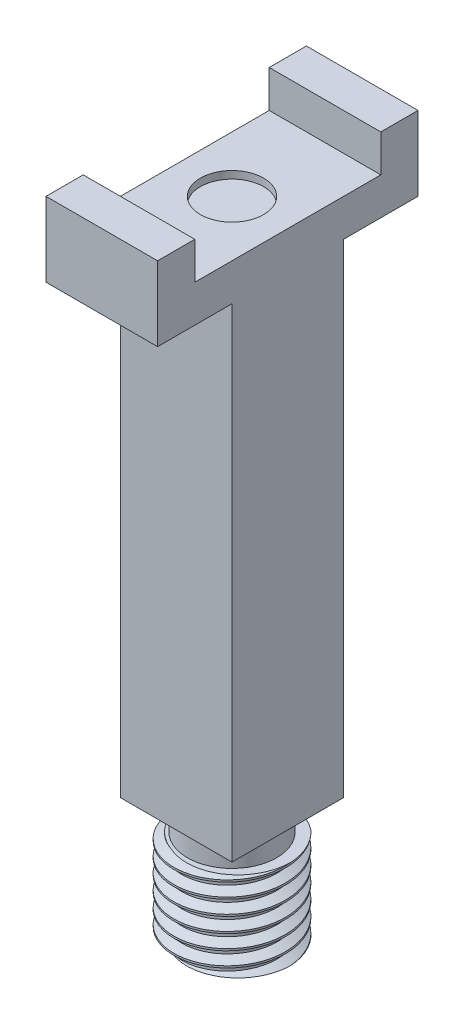
SolidWorks part; units mm, degrees
ref_plane "Piano frontale" through (0, 0, 0) normal (0, 0, 1) x (1, 0, 0)
ref_plane "Piano superiore" through (0, 0, 0) normal (0, 1, 0) x (1, 0, 0)
ref_plane "Piano destro" through (0, 0, 0) normal (1, 0, 0) x (0, 0, -1)
sketch "Schizzo1" plane through (0, 0, 0) normal (0, 1, 0) x (1, 0, 0)
  line L0 (0, 50.9857) -> (0, -54.0167) construction
  line L1 (-65.0582, 0) -> (55.7487, 0) construction
  line L3 (-7.5, 7.5) -> (7.5, 7.5)
  line L4 (-7.5, 7.5) -> (-7.5, -7.5)
  line L5 (-7.5, -7.5) -> (7.5, -7.5)
  line L6 (7.5, 7.5) -> (7.5, -7.5)
  line L7 (-7.5, 7.5) -> (7.5, -7.5) construction
  line L8 (-7.5, -7.5) -> (7.5, 7.5) construction
  point P5 (0, 0)
  dimension "D1" = 15
extrude "Estrusione-Estrusione1" add sketch "Schizzo1" along normal blind 70
sketch "Schizzo2" plane through (0, 0, 7.5) normal (0, 0, 1) x (1, 0, 0)
  line L0 (7.5, 70) -> (7.5, 0) construction
  line L1 (-7.5, 70) -> (7.5, 70)
  line L2 (-7.5, 70) -> (-7.5, 65)
  line L3 (-7.5, 65) -> (7.5, 65)
  line L4 (7.5, 70) -> (7.5, 65)
  dimension "D1" = 5
extrude "Estrusione-Estrusione2" add sketch "Schizzo2" along normal blind 10 contours L2 L1 L4 L3
sketch "Schizzo3" plane through (0, 70, 0) normal (0, 1, 0) x (1, 0, 0)
  line L0 (7.5, -17.5) -> (7.5, 7.5) construction
  line L1 (-7.5, -17.5) -> (7.5, -17.5)
  line L2 (-7.5, -17.5) -> (-7.5, -12.5)
  line L3 (-7.5, -12.5) -> (7.5, -12.5)
  line L4 (7.5, -17.5) -> (7.5, -12.5)
  dimension "D1" = 5
extrude "Estrusione-Estrusione3" add sketch "Schizzo3" along normal blind 5
ref_plane "Piano1" through (0, 0, 0) normal (0, 0, -1) x (-1, 0, 0)
mirror "Specchia1" about plane through (0, 0, 0) normal (0, 0, -1) of "Estrusione-Estrusione2", "Estrusione-Estrusione1", "Estrusione-Estrusione3"
sketch "Sketch1" plane through (0, 0, 0) normal (0, -1, 0) x (1, 0, 0)
  circle A0 centre (0, 0) radius 6
  dimension "D1" = 12
extrude "Boss-Extrude1" add sketch "Sketch1" along normal blind 4
sketch "Sketch11" plane through (0, -4, 0) normal (0, -1, 0) x (1, 0, 0)
  circle A0 centre (0, 0) radius 7.5
  dimension "D1" = 15
extrude "Boss-Extrude2" add sketch "Sketch11" along normal blind 12
thread "Thread2" pitch 2 method cut trim with start face yes trim with end face yes profile "Thread Profile2" start angle 3, offset 2, length 15, pitch 2, diameter 15
ref_plane "Plane6" through (7.4897, -18, -0.3925) normal (0.0523, 0, 0.9986) x (0.9986, 0, -0.0523)
sketch "Thread Profile2" plane through (7.4897, -18, -0.3925) normal (0.0523, 0, 0.9986) x (0.9986, 0, -0.0523)
  line L0 (0, 0) -> (0, 2) construction
  line L11 (0, 0) -> (0, 1.75)
  line L12 (0, 1.75) -> (-1.0825, 1.125)
  line L13 (-1.0825, 1.125) -> (-1.0825, 0.625)
  line L15 (-1.0825, 0.625) -> (0, 0)
  line L17 (-1.0825, 0.875) -> (0, 0.875) construction
  point P2 (0, 0)
  dimension "Pitch" = 2
  dimension "Profile_Angle" = 60
  dimension "Profile_Land" = 0.5
  dimension "Profile_Height" = 1.0825
sketch "Sketch12" plane through (0, 70, 0) normal (0, 1, 0) x (1, 0, 0)
  circle A0 centre (0, 0) radius 4.25
  dimension "D1" = 8.5
extrude "Cut-Extrude1" cut sketch "Sketch12" against normal blind 1
